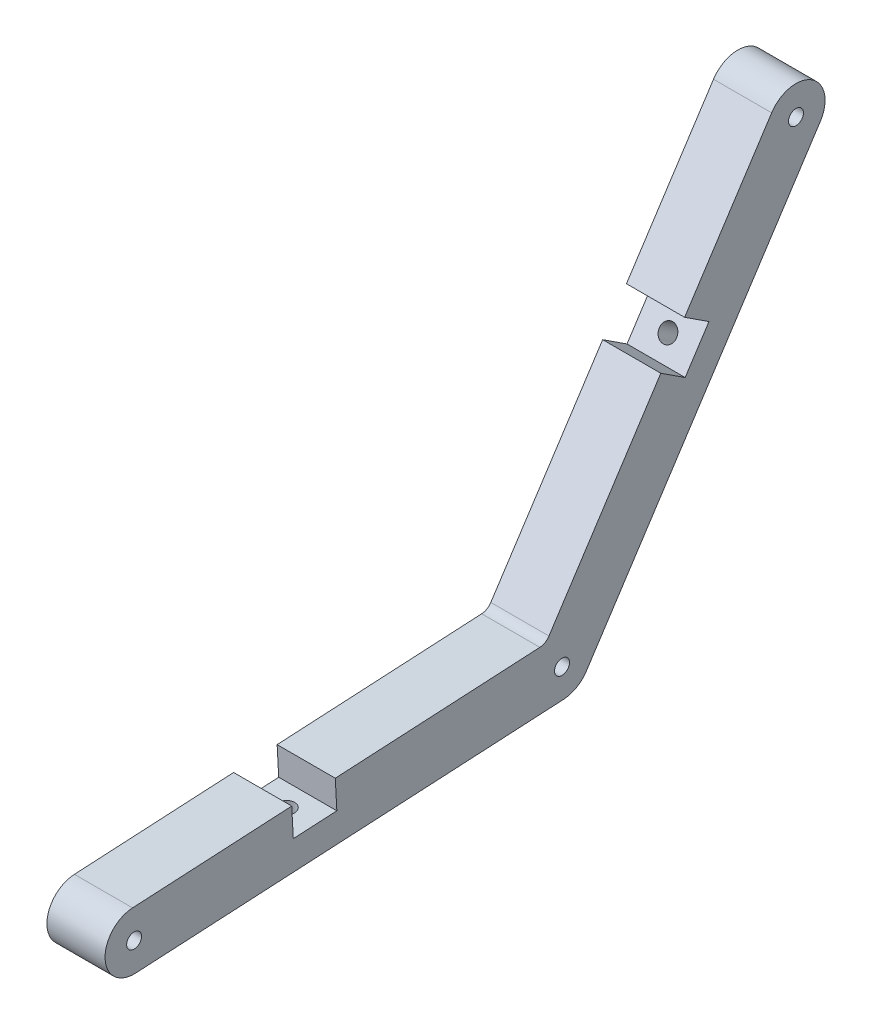
SolidWorks part; units mm, degrees
material "Custom Plastic"
ref_plane "Front Plane" through (0, 0, 0) normal (0, 0, 1) x (1, 0, 0)
ref_plane "Top Plane" through (0, 0, 0) normal (0, 1, 0) x (1, 0, 0)
ref_plane "Right Plane" through (0, 0, 0) normal (1, 0, 0) x (0, 0, -1)
sketch "Sketch1" plane through (0, 0, 0) normal (1, 0, 0) x (0, 0, -1)
  line L0 (60.5924, 72.9491) -> (13.8564, -8) construction
  line L1 (0, -16) -> (-93.472, -16) construction
  line L2 (-93.8143, 1.2945) -> (-3.5605, 6.167)
  line L3 (-93.1297, -11.387) -> (0.3423, -6.3408)
  line L4 (-3.5605, 6.167) -> (45.7861, 81.8928)
  line L5 (56.4263, 74.9592) -> (5.3201, -3.4668)
  line L6 (-3.5605, 6.167) -> (-0.3423, 6.3408) construction
  line L7 (-3.5605, 6.167) -> (-5.3201, 3.4668) construction
  circle A0 centre (0, 0) radius 16 construction
  circle A1 centre (51.1062, 78.426) radius 10.9537 construction
  circle A2 centre (-93.472, -5.0463) radius 10.9538 construction
  arc A3 (-93.8143, 1.2945) -> (-93.1297, -11.387) centre (-93.472, -5.0463) ccw
  arc A4 (0.3423, -6.3408) -> (5.3201, -3.4668) centre (0, 0) ccw
  arc A5 (56.4263, 74.9592) -> (45.7861, 81.8928) centre (51.1062, 78.426) ccw
  dimension "D3" = 21.9075
  dimension "D4" = 32
  dimension "D5" = 12.7
  dimension "D1" = 120
  dimension "D2" = 93.472
extrude "Boss-Extrude1" add sketch "Sketch1" along normal blind 12.7
sketch "Sketch2" plane through (12.7, 0, 0) normal (1, 0, 0) x (0, 0, -1)
  line L0 (-54.2867, 3.4285) -> (-53.602, -9.253) construction
  line L1 (-3.5605, 6.167) -> (-93.8143, 1.2945) construction
  line L2 (-93.1297, -11.387) -> (0.3423, -6.3408) construction
  line L3 (24.1742, 48.7279) -> (34.8144, 41.7942) construction
  line L4 (45.7861, 81.8928) -> (-3.5605, 6.167) construction
  line L5 (5.3201, -3.4668) -> (56.4263, 74.9592) construction
  line L6 (-59.0422, 3.1717) -> (-58.6999, -3.169)
  line L7 (-58.6999, -3.169) -> (-49.1888, -2.6555)
  line L8 (-49.1888, -2.6555) -> (-49.5311, 3.6852)
  line L9 (21.574, 44.7378) -> (26.8942, 41.271)
  line L10 (26.8942, 41.271) -> (32.0944, 49.2511)
  line L11 (32.0944, 49.2511) -> (26.7743, 52.718)
  line L12 (-59.0422, 3.1717) -> (-49.5311, 3.6852)
  line L13 (26.7743, 52.718) -> (21.574, 44.7378)
  point P15 (-53.9443, -2.9123)
  point P21 (29.4943, 45.261)
  dimension "D1" = 9.525
  dimension "D2" = 9.525
  dimension "D3" = 50.8
  dimension "D4" = 50.8
extrude "Cut-Extrude1" cut sketch "Sketch2" against normal through all
hole_wizard "Axel Holes" positions "3DSketch1" profile "Sketch3" hole size "#4" standard "ANSI Inch" end condition through all
sketch3d "3DSketch1"
  line L0 (12.7, -5.0463, 93.472) -> (0, -5.0463, 93.472) construction
  line L1 (12.7, 78.426, -51.1062) -> (0, 78.426, -51.1062) construction
  arc A0 (12.7, -6.3408, -0.3423) -> (12.7, -3.4668, -5.3201) centre (12.7, 0, 0) ccw construction
  point P0 (12.7, -5.0463, 93.472)
  point P4 (12.7, 0, 0)
  point P6 (12.7, 78.426, -51.1062)
  point P15 (19.05, 0, 0)
sketch "Sketch3" plane through (12.7, -5.0463, 93.472) normal (0, 1, 0) x (0, 0, -1)
  line L0 (0, 0) -> (0, 12.7)
  line L1 (0, 12.7) -> (1.6319, 12.7)
  line L2 (1.6319, 12.7) -> (1.6319, 0)
  line L5 (1.6319, 0) -> (0, 0)
  line L11 (0, -6.35) -> (0, 107.95) construction
  dimension "Thru Hole Dia." = 3.2639
  dimension "Thru Hole Depth" = 12.7
hole_wizard "Mounting Holes" positions "3DSketch4" profile "Sketch5" hole size "#6" standard "ANSI Inch" end condition through all
sketch3d "3DSketch4"
  line L0 (0, -2.6555, 49.1888) -> (12.7, -3.169, 58.6999) construction
  line L2 (0, 41.271, -26.8942) -> (12.7, 49.2511, -32.0944) construction
  point P0 (6.35, -2.9123, 53.9443)
  point P2 (6.35, 45.261, -29.4943)
  point P11 (6.35, -2.9123, 53.9443)
  point P18 (6.35, 45.261, -29.4943)
sketch "Sketch5" plane through (6.35, -2.9123, 53.9443) normal (1, 0, 0) x (0, -0.0539, 0.9985)
  line L0 (0, 0) -> (0, 14.477)
  line L1 (0, 14.477) -> (1.8986, 14.477)
  line L2 (1.8986, 14.477) -> (1.8986, 0)
  line L5 (1.8986, 0) -> (0, 0)
  line L11 (0, -6.35) -> (0, 107.95) construction
  dimension "Thru Hole Dia." = 3.7973
  dimension "Thru Hole Depth" = 14.477
fillet "Fillet1" radius 2.54 1 edges at (6.35, 6.167, 3.5605)
equation "\"D2@Sketch2\"=\"D1@Sketch2\""
equation "\"D4@Sketch2\"=\"D3@Sketch2\""
